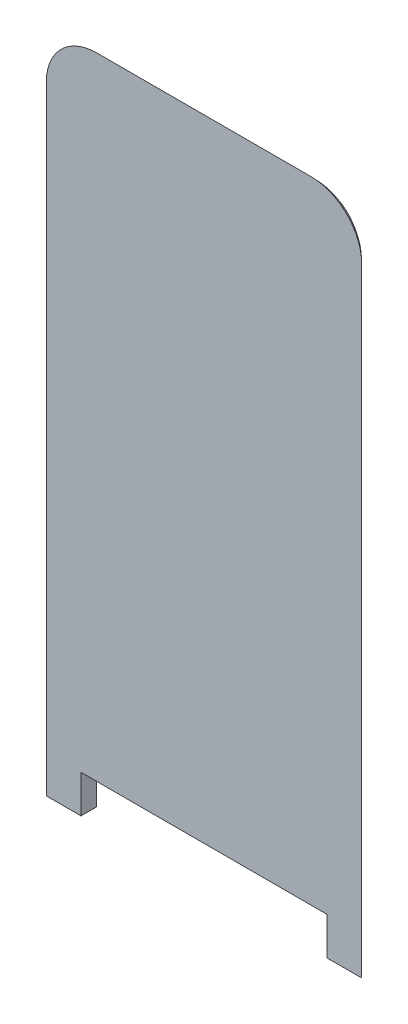
SolidWorks part; units mm, degrees
ref_plane "Front Plane" through (0, 0, 0) normal (0, 0, 1) x (1, 0, 0)
ref_plane "Top Plane" through (0, 0, 0) normal (0, 1, 0) x (1, 0, 0)
ref_plane "Right Plane" through (0, 0, 0) normal (1, 0, 0) x (0, 0, -1)
sketch "Sketch1" plane through (0, 0, 0) normal (0, 0, 1) x (1, 0, 0)
  line L0 (19.5, -53) -> (25, -53)
  line L1 (-25, 53) -> (25, 53)
  line L2 (-25, 53) -> (-25, -53)
  line L3 (-25, -53) -> (-19.5, -53)
  line L4 (25, 53) -> (25, -53)
  line L5 (-25, 53) -> (25, -53) construction
  line L6 (-25, -53) -> (25, 53) construction
  line L8 (-19.5, -53) -> (-19.5, -47.0173)
  line L9 (-19.5, -47.0173) -> (19.5, -47.0173)
  line L10 (19.5, -53) -> (19.5, -47.0173)
  point P0 (0, 0)
  dimension "D1" = 50
  dimension "D2" = 106
  dimension "D3" = 5.5
  dimension "D4" = 5.5
extrude "Boss-Extrude1" add sketch "Sketch1" along normal blind 2.5
fillet "Fillet1" radius 8 2 edges at (25, 53, 1.25) (-25, 53, 1.25)
fillet "Fillet2" radius 8 5 edges at (-25, -4, 0) (-22.6569, 50.6569, 0) (0, 53, 0) (22.6569, 50.6569, 0) (25, -4, 0)
